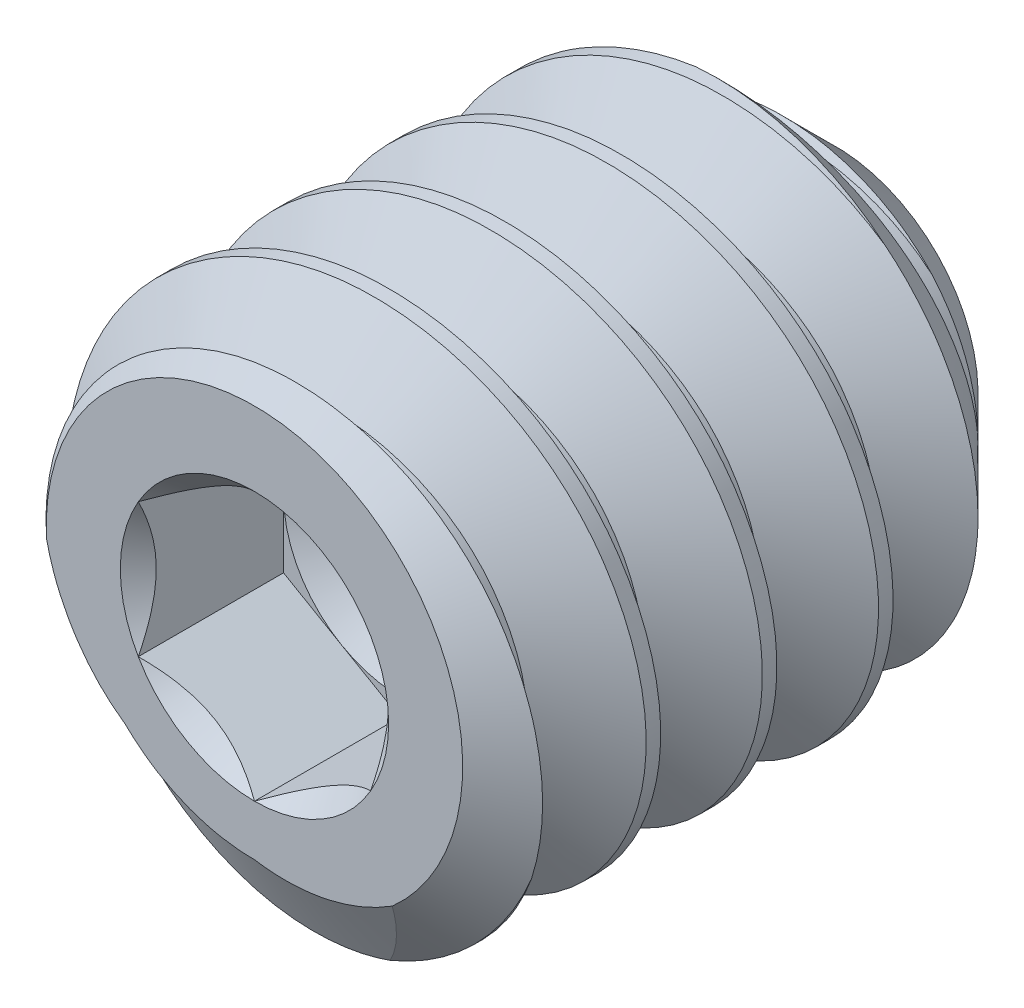
SolidWorks part; units mm, degrees
ref_plane "Front" through (0, 0, 0) normal (0, 0, 1) x (1, 0, 0)
ref_plane "Top" through (0, 0, 0) normal (0, 1, 0) x (1, 0, 0)
ref_plane "Right" through (0, 0, 0) normal (1, 0, 0) x (0, 0, -1)
sketch "Sketch22" plane through (0, 0, 0) normal (1, 0, 0) x (0, 0, -1)
  line L0 (-1.3533, 0) -> (-1.3533, 1.1379)
  line L1 (-1.3533, 1.1379) -> (-1.1541, 1.4224)
  line L2 (-1.1541, 1.4224) -> (1.1787, 1.4224)
  line L3 (1.1787, 1.4224) -> (1.8217, 0.7794)
  line L4 (1.8217, 0.7794) -> (1.3533, 0) construction
  line L5 (1.3533, 0) -> (-1.3533, 0)
  line L6 (1.3533, 0) -> (1.8217, 0) construction
  line L7 (1.8217, 0) -> (1.8217, 0.7794) construction
  line L8 (1.8217, -0.7794) -> (1.3533, 0) construction
  line L9 (-1.1541, -1.4224) -> (1.1787, -1.4224) construction
  line L10 (1.8217, 0.7794) -> (1.8217, 0)
  line L11 (1.8217, 0) -> (1.3533, 0)
  dimension "Dia" = 2.8448
  dimension "Length" = 3.175
  dimension "D3" = 35
  dimension "D5" = 118
  dimension "D6" = 45
  dimension "D7" = 2.2758
revolve "Revolve1" add sketch "Sketch22" angle 360 about L6
ref_plane "Plane1" through (0, 0, -1.8217) normal (0, 0, 1) x (1, 0, 0)
sketch "Sketch27" plane through (0, 0, -1.8217) normal (0, 0, 1) x (1, 0, 0)
  circle A0 centre (0, 0) radius 1.4224 construction
  circle A1 centre (0, 0) radius 1.4224
curve "Helix/Spiral1" pitch 0.635 height 3.81 radius 1.4224 centre (0, 0, -1.8217) axis (0, 0, 1) start towards (0, 1, 0)
sketch "Sketch28" plane through (0, 0, 0) normal (1, 0, 0) x (0, 0, -1)
  line L0 (1.8217, 1.4224) -> (2.3773, 1.4224)
  line L1 (2.3773, 1.4224) -> (2.1392, 1.01)
  line L2 (2.1392, 1.01) -> (2.0598, 1.01)
  line L3 (2.0598, 1.01) -> (1.8217, 1.4224)
  line L4 (1.9407, 1.2162) -> (2.2582, 1.2162) construction
  line L6 (-1.1541, 1.4224) -> (1.1787, 1.4224) construction
  line L7 (1.8217, 6.985) -> (1.8217, -6.985) construction
  dimension "D1" = 0.0794
  dimension "D3" = 60
  dimension "D2" = 0.3175
sweep "Cut-Sweep2" cut profiles "Sketch28" path "Helix/Spiral1" align with end faces yes
sketch "Sketch23" plane through (0, 0, 1.3533) normal (0, 0, 1) x (1, 0, 0)
  line L1 (0, 0.7332) -> (-0.635, 0.3666)
  line L2 (-0.635, 0.3666) -> (-0.635, -0.3666)
  line L3 (-0.635, -0.3666) -> (0, -0.7332)
  line L4 (0, -0.7332) -> (0.635, -0.3666)
  line L5 (0.635, -0.3666) -> (0.635, 0.3666)
  line L6 (0.635, 0.3666) -> (0, 0.7332)
  circle A0 centre (0, 0) radius 0.635 construction
  dimension "Hex" = 1.27
extrude "Cut-Extrude10" cut sketch "Sketch23" against normal blind 0.7937
sketch "Sketch24" plane through (0, 0, 1.3533) normal (0, 0, 1) x (1, 0, 0)
  circle A0 centre (0, 0) radius 0.7332
extrude "Cut-Extrude11" cut sketch "Sketch24" against normal through all draft 45
sketch "Sketch26" plane through (0, 0, 0.5596) normal (0, 0, 1) x (1, 0, 0)
  circle A0 centre (0, 0) radius 0.635 construction
  circle A1 centre (0, 0) radius 0.635
extrude "Cut-Extrude12" cut sketch "Sketch26" against normal through all draft 60
sketch "Sketch30" plane through (0, 0, 0) normal (1, 0, 0) x (0, 0, -1)
  line L0 (-1.1541, 1.4224) -> (1.1787, 1.4224) construction
  line L1 (-1.3533, 0) -> (-1.3533, 1.1379) construction
  line L2 (1.8217, 0) -> (1.8217, 0.7794) construction
  line L3 (-1.1541, -1.4224) -> (1.1787, -1.4224) construction
  point P0 (-1.3533, 1.4224)
  point P1 (1.8217, 1.4224)
  point P2 (1.8217, -1.4224)
  point P11 (-0.4008, -1.4224)
  dimension "D1" = 2.2225
sketch "Sketch31" plane through (0, 0, 0) normal (1, 0, 0) x (0, 0, -1)
  line L2 (1.3533, 0) -> (1.8217, -0.7794)
  line L3 (1.8217, 0.7794) -> (1.3533, 0)
equation "\"D7@Sketch22\"=\"Dia@Sketch22\"*.8"
equation "\"D1@Sketch28\" = \"D4@Helix/Spiral1\" * .125"
equation "\"D3@Helix/Spiral1\" = \"Length@Sketch22\" + \"D4@Helix/Spiral1\""
equation "\"D1@Sketch30\" = \"D4@Helix/Spiral1\" * 3.5"
equation "\"hex Depth@Cut-Extrude10\" = \"Hex@Sketch23\" * .625"
equation "\"D2@Sketch28\" = \"D4@Helix/Spiral1\" * .5"
